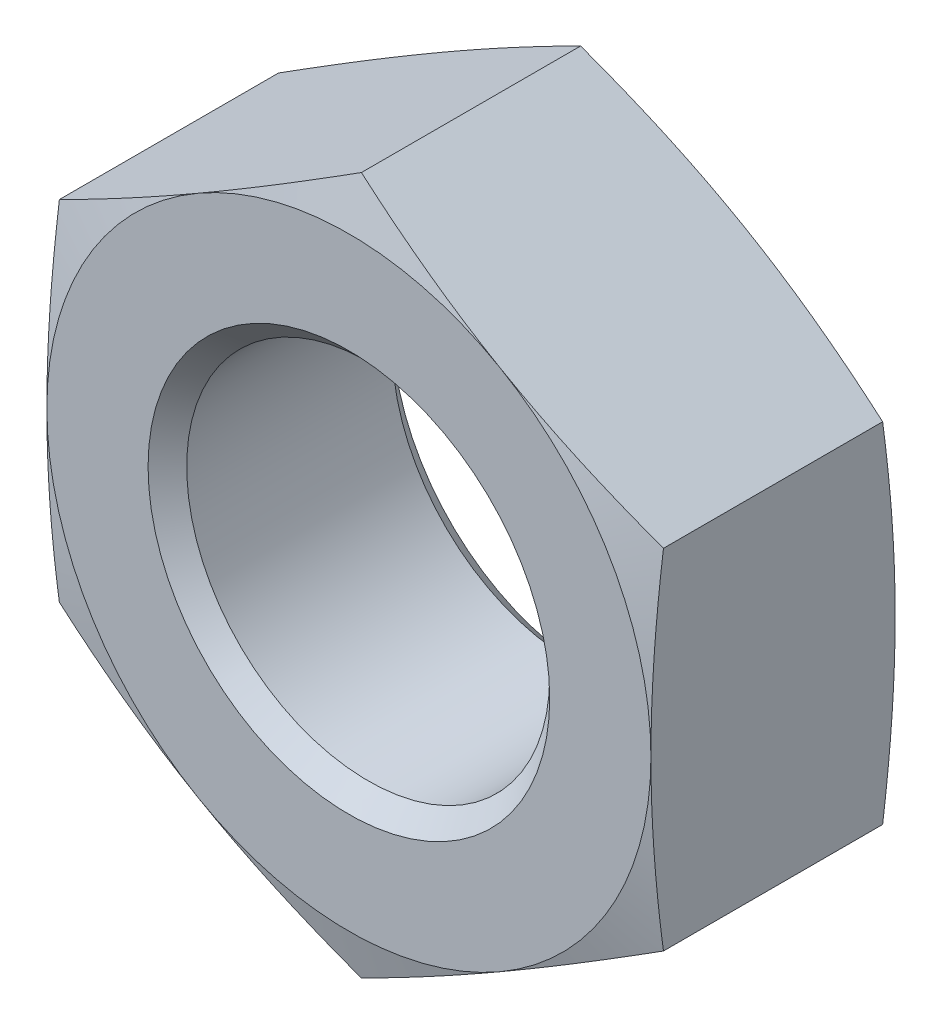
SolidWorks part; units mm, degrees
material "Cast Alloy Steel"
ref_plane "Front Plane" through (0, 0, 0) normal (0, 0, 1) x (1, 0, 0)
ref_plane "Top Plane" through (0, 0, 0) normal (0, 1, 0) x (1, 0, 0)
ref_plane "Right Plane" through (0, 0, 0) normal (1, 0, 0) x (0, 0, -1)
sketch "Sketch1" plane through (0, 0, 0) normal (1, 0, 0) x (0, 0, -1)
  line L0 (0, 0) -> (0, 11.938)
  line L1 (0, 11.938) -> (0.6398, 14.3256)
  line L2 (0.6398, 14.3256) -> (9.0122, 14.3256)
  line L3 (9.0122, 14.3256) -> (9.652, 11.938)
  line L4 (9.652, 11.938) -> (9.652, 0)
  line L5 (9.652, 0) -> (0, 0)
  line L6 (9.652, 0) -> (0, 0) construction
sketch "Sketch2" plane through (0, 0, 0) normal (0, 0, 1) x (1, 0, 0)
  line L0 (-23.876, 23.876) -> (-23.876, -23.876)
  line L1 (-23.876, -23.876) -> (23.876, -23.876)
  line L2 (23.876, -23.876) -> (23.876, 23.876)
  line L3 (23.876, 23.876) -> (-23.876, 23.876)
  line L4 (-11.938, 6.8924) -> (-11.938, -6.8924)
  line L5 (-11.938, -6.8924) -> (0, -13.7848)
  line L6 (0, -13.7848) -> (11.938, -6.8924)
  line L7 (11.938, -6.8924) -> (11.938, 6.8924)
  line L8 (11.938, 6.8924) -> (0, 13.7848)
  line L9 (0, 13.7848) -> (-11.938, 6.8924)
revolve "Revolve1" add sketch "Sketch1" angle 360 about L6 reverse direction yes
extrude "Cut-Extrude1" cut sketch "Sketch2" against normal blind 9.652
sketch "Sketch3" plane through (0, 0, 0) normal (1, 0, 0) x (0, 0, -1)
  line L0 (0, 0) -> (0, 7.9375)
  line L1 (0, 7.9375) -> (0.7633, 7.1742)
  line L2 (0.7633, 7.1742) -> (8.8887, 7.1742)
  line L3 (8.8887, 7.1742) -> (9.652, 7.9375)
  line L4 (9.652, 7.9375) -> (9.652, 0)
  line L5 (9.652, 0) -> (0, 0)
  line L6 (9.652, 0) -> (0, 0) construction
revolve "Cut-Revolve1" cut sketch "Sketch3" angle 360 about L6 reverse direction yes
cosmetic thread "Cosmetic Thread1" parameters "D1"=9.652, "D2"=15.875
ref_plane "NUT XY" through (0, 0, 0) normal (0, 0, 1) x (1, 0, 0)
ref_plane "NUT XZ" through (0, 0, 0) normal (0, -1, 0) x (-1, 0, 0)
ref_plane "NUT YZ" through (0, 0, 0) normal (1, 0, 0) x (0, 0, -1)
ref_axis "NUT X" through (-80.9, 0, 0) along (1, 0, 0)
ref_axis "NUT Y" through (0, -50, 0) along (0, 1, 0)
ref_axis "NUT Z" through (0, 0, 80.9) along (0, 0, -1)
sketch3d "NUT"
  point P0 (0, 0, 0)
ref_plane "a1 XY" through (0, 0, 0) normal (0, 0, 1) x (1, 0, 0)
ref_plane "a1 XZ" through (0, 11.938, 0) normal (0, -1, 0) x (-1, 0, 0)
ref_plane "a1 YZ" through (-11.938, 0, 0) normal (1, 0, 0) x (0, 0, -1)
ref_axis "a1 X" through (-80.9, 11.938, 0) along (1, 0, 0)
ref_axis "a1 Y" through (-11.938, -50, 0) along (0, 1, 0)
ref_axis "a1 Z" through (-11.938, 11.938, 80.9) along (0, 0, -1)
sketch3d "a1"
  point P0 (-11.938, 11.938, 0)
ref_plane "a2 XY" through (0, 0, 0) normal (0, 0, 1) x (1, 0, 0)
ref_plane "a2 XZ" through (0, 11.938, 0) normal (0, -1, 0) x (-1, 0, 0)
ref_plane "a2 YZ" through (11.938, 0, 0) normal (1, 0, 0) x (0, 0, -1)
ref_axis "a2 X" through (-80.9, 11.938, 0) along (1, 0, 0)
ref_axis "a2 Y" through (11.938, -50, 0) along (0, 1, 0)
ref_axis "a2 Z" through (11.938, 11.938, 80.9) along (0, 0, -1)
sketch3d "a2"
  point P0 (11.938, 11.938, 0)
ref_plane "b1 XY" through (0, 0, 0) normal (1, 0, 0) x (0, 0, -1)
ref_plane "b1 XZ" through (0, 11.938, 0) normal (0, -1, 0) x (-1, 0, 0)
ref_plane "b1 YZ" through (0, 0, 0) normal (0, 0, -1) x (-1, 0, 0)
ref_axis "b1 X" through (0, 11.938, 80.9) along (0, 0, -1)
ref_axis "b1 Y" through (0, -50, 0) along (0, 1, 0)
ref_axis "b1 Z" through (80.9, 11.938, 0) along (-1, 0, 0)
sketch3d "b1"
  point P0 (0, 11.938, 0)
ref_plane "b2 XY" through (0, 0, 0) normal (1, 0, 0) x (0, 0, -1)
ref_plane "b2 XZ" through (0, 11.938, 0) normal (0, -1, 0) x (-1, 0, 0)
ref_plane "b2 YZ" through (0, 0, -9.652) normal (0, 0, -1) x (-1, 0, 0)
ref_axis "b2 X" through (0, 11.938, 80.9) along (0, 0, -1)
ref_axis "b2 Y" through (0, -50, -9.652) along (0, 1, 0)
ref_axis "b2 Z" through (80.9, 11.938, -9.652) along (-1, 0, 0)
sketch3d "b2"
  point P0 (0, 11.938, -9.652)
ref_plane "e XY" through (0, 0, 0) normal (1, 0, 0) x (0, 0, -1)
ref_plane "e XZ" through (0, 0, 0) normal (0, -1, 0) x (-1, 0, 0)
ref_plane "e YZ" through (0, 0, -9.652) normal (0, 0, -1) x (-1, 0, 0)
ref_axis "e X" through (0, 0, 80.9) along (0, 0, -1)
ref_axis "e Y" through (0, -50, -9.652) along (0, 1, 0)
ref_axis "e Z" through (80.9, 0, -9.652) along (-1, 0, 0)
sketch3d "e"
  point P0 (0, 0, -9.652)
ref_plane "ol1 XY" through (0, 0, 0) normal (0, 1, 0) x (1, 0, 0)
ref_plane "ol1 XZ" through (0, 0, -11.938) normal (0, 0, 1) x (1, 0, 0)
ref_plane "ol1 YZ" through (0, 0, 0) normal (1, 0, 0) x (0, 0, -1)
ref_axis "ol1 X" through (-80.9, 0, -11.938) along (1, 0, 0)
ref_axis "ol1 Y" through (0, 0, 50) along (0, 0, -1)
ref_axis "ol1 Z" through (0, 50, -11.938) along (0, -1, 0)
sketch3d "ol1"
  point P0 (0, 0, -11.938)
ref_plane "ol2 XY" through (0, 0, 0) normal (0, 1, 0) x (1, 0, 0)
ref_plane "ol2 XZ" through (0, 0, -11.938) normal (0, 0, 1) x (1, 0, 0)
ref_plane "ol2 YZ" through (9.652, 0, 0) normal (1, 0, 0) x (0, 0, -1)
ref_axis "ol2 X" through (-80.9, 0, -11.938) along (1, 0, 0)
ref_axis "ol2 Y" through (9.652, 0, 50) along (0, 0, -1)
ref_axis "ol2 Z" through (9.652, 50, -11.938) along (0, -1, 0)
sketch3d "ol2"
  point P0 (9.652, 0, -11.938)
ref_plane "th1 XY" through (0, 0, 0) normal (1, 0, 0) x (0, 0, -1)
ref_plane "th1 XZ" through (0, 7.9375, 0) normal (0, -1, 0) x (-1, 0, 0)
ref_plane "th1 YZ" through (0, 0, -9.652) normal (0, 0, -1) x (-1, 0, 0)
ref_axis "th1 X" through (0, 7.9375, 80.9) along (0, 0, -1)
ref_axis "th1 Y" through (0, -50, -9.652) along (0, 1, 0)
ref_axis "th1 Z" through (80.9, 7.9375, -9.652) along (-1, 0, 0)
sketch3d "th1"
  point P0 (0, 7.9375, -9.652)
ref_plane "th2 XY" through (0, 0, 0) normal (1, 0, 0) x (0, 0, -1)
ref_plane "th2 XZ" through (0, -7.9375, 0) normal (0, -1, 0) x (-1, 0, 0)
ref_plane "th2 YZ" through (0, 0, -9.652) normal (0, 0, -1) x (-1, 0, 0)
ref_axis "th2 X" through (0, -7.9375, 80.9) along (0, 0, -1)
ref_axis "th2 Y" through (0, -50, -9.652) along (0, 1, 0)
ref_axis "th2 Z" through (80.9, -7.9375, -9.652) along (-1, 0, 0)
sketch3d "th2"
  point P0 (0, -7.9375, -9.652)
